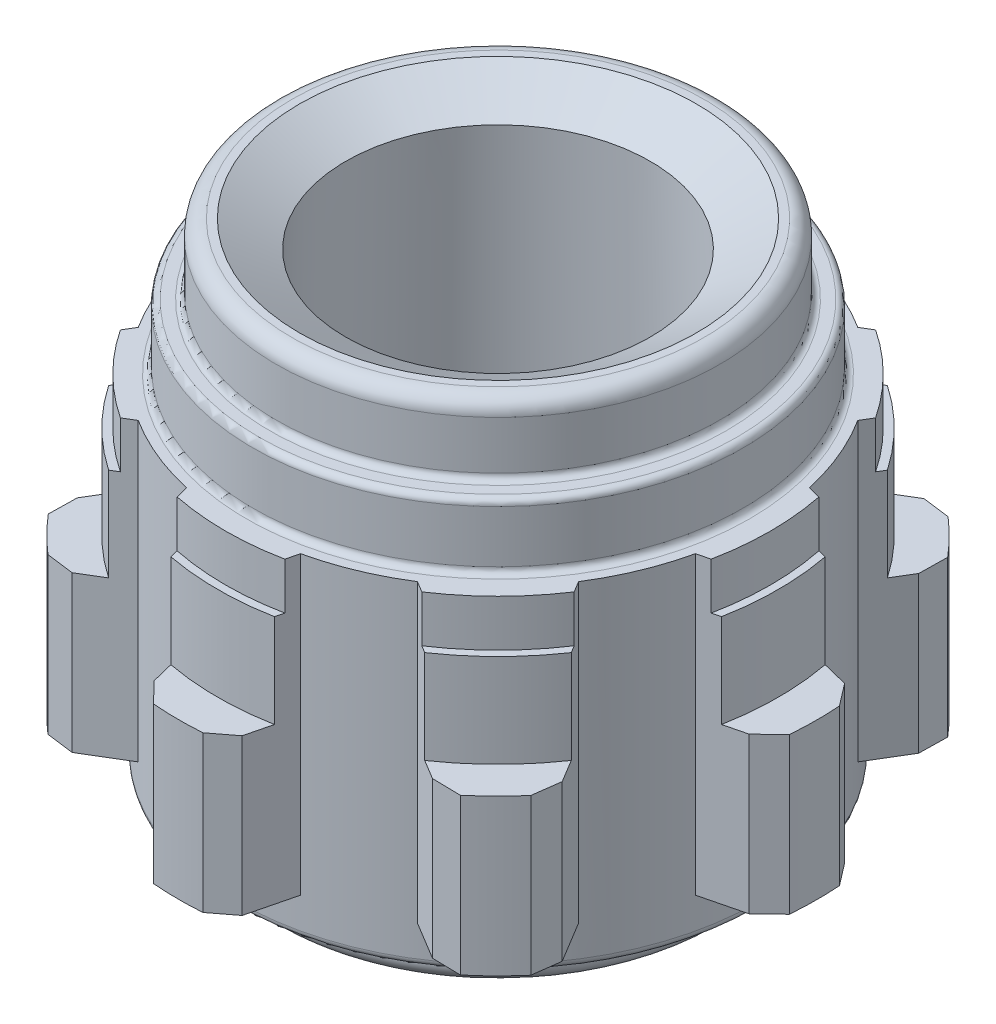
SolidWorks part; units mm, degrees
other "Câmera1"
ref_plane "Plano frontal" through (0, 0, 0) normal (0, 0, 1) x (1, 0, 0)
ref_plane "Plano superior" through (0, 0, 0) normal (0, 1, 0) x (1, 0, 0)
ref_plane "Plano direito" through (0, 0, 0) normal (1, 0, 0) x (0, 0, -1)
sketch "Esboço1" plane through (0, 0, 0) normal (0, 0, 1) x (1, 0, 0)
  line L0 (20.9097, -57.0834) -> (20.9097, 23.3) construction
  line L1 (40.4097, 23.3) -> (49.4097, 23.3)
  line L2 (49.4097, 23.3) -> (49.4097, 14.3)
  line L3 (49.4097, 14.3) -> (52.4097, 14.3)
  line L4 (52.4097, 14.3) -> (52.4097, 6)
  line L5 (52.4097, 6) -> (55.9097, 6)
  line L6 (55.9097, 6) -> (55.9097, 0)
  line L7 (55.9097, 0) -> (56.9097, 0)
  line L8 (56.9097, 0) -> (56.9097, -12)
  line L9 (56.9097, -12) -> (61.9097, -12)
  line L10 (61.9097, -12) -> (61.9097, -32)
  line L11 (61.9097, -32) -> (54.4097, -32)
  line L12 (54.4097, -32) -> (54.4097, -37)
  line L13 (54.4097, -37) -> (49.4097, -37)
  line L14 (49.4097, -37) -> (49.4097, -42)
  line L15 (49.4097, -42) -> (41.7996, -42)
  line L16 (41.7996, -42) -> (40.4097, 23.3)
  dimension "D1" = 19.5
  dimension "D2" = 28.5
  dimension "D3" = 31.5
  dimension "D4" = 35
  dimension "D5" = 36
  dimension "D6" = 41
  dimension "D7" = 33.5
  dimension "D8" = 28.5
  dimension "D9" = 9
  dimension "D10" = 8.3
  dimension "D11" = 6
  dimension "D12" = 12
  dimension "D13" = 20
  dimension "D14" = 5
  dimension "D15" = 5
revolve "Revolução1" add sketch "Esboço1" angle 360 about L0
sketch "Esboço2" plane through (0, -32, 0) normal (0, -1, 0) x (1, 0, 0)
  line L0 (20.9097, 0) -> (-27.9425, 0) construction
  line L1 (-20.1424, -5.25) -> (-20.1424, 5.25)
  line L2 (-20.1424, -5.25) -> (-11.6715, -7.35)
  line L3 (-11.8308, 25.3159) -> (-4.4062, 32.7405)
  line L4 (-20.1424, 5.25) -> (-11.6715, 7.35)
  line L5 (-4.4062, 32.7405) -> (3.0685, 28.2357)
  line L6 (-11.8308, 25.3159) -> (-7.3259, 17.8412)
  line L7 (15.6597, 41.0521) -> (26.1597, 41.0521)
  line L8 (26.1597, 41.0521) -> (28.2597, 32.5812)
  line L9 (15.6597, 41.0521) -> (13.5597, 32.5812)
  line L10 (46.2256, 32.7405) -> (53.6503, 25.3159)
  line L11 (53.6503, 25.3159) -> (49.1454, 17.8412)
  line L12 (46.2256, 32.7405) -> (38.7509, 28.2357)
  line L13 (61.9618, 5.25) -> (61.9618, -5.25)
  line L14 (61.9618, -5.25) -> (53.491, -7.35)
  line L15 (61.9618, 5.25) -> (53.491, 7.35)
  line L16 (53.6503, -25.3159) -> (46.2256, -32.7405)
  line L17 (46.2256, -32.7405) -> (38.7509, -28.2357)
  line L18 (53.6503, -25.3159) -> (49.1454, -17.8412)
  line L19 (26.1597, -41.0521) -> (15.6597, -41.0521)
  line L20 (15.6597, -41.0521) -> (13.5597, -32.5812)
  line L21 (26.1597, -41.0521) -> (28.2597, -32.5812)
  line L22 (-4.4062, -32.7405) -> (-11.8308, -25.3159)
  line L23 (-11.8308, -25.3159) -> (-7.3259, -17.8412)
  line L24 (-4.4062, -32.7405) -> (3.0685, -28.2357)
  circle A0 centre (20.9097, 0) radius 33.4
  circle M1 centre (20.9097, 0) radius 41
  circle M2 centre (20.9097, 0) radius 33.5
  dimension "D1" = 8
  dimension "D2" = 10.5
extrude "Corte-extrusão3" cut sketch "Esboço2" against normal through all contours L6 L4 M1 M2 | L9 L5 M1 M2 | L12 L8 M1 M2 | L15 L11 M1 M2 | L18 L14 M1 M2 | L21 L17 M1 M2 | L24 L20 M1 M2 | L23 L2 M1 M2
chamfer "Chanfro1" distance 2.5 angle 30 18 edges at (20.9097, -32, -41) (26.2595, -22, -40.6495) (20.9097, -12, -41) (15.5599, -22, -40.6495) (53.4361, -22, 24.9606) (45.8704, -22, 32.5264) (15.5599, -22, 40.6495) (26.2595, -22, 40.6495) (-4.0509, -22, 32.5264) (-11.6167, -22, 24.9606) (-19.7397, -22, 5.3498) (-19.7397, -22, -5.3498) (-11.6167, -22, -24.9606) (-4.0509, -22, -32.5264) (61.5592, -22, 5.3498) (61.5592, -22, -5.3498) (53.4361, -22, -24.9606) (45.8704, -22, -32.5264)
chamfer "Chanfro2" distance 6 angle 30 1 edges at (40.4097, 23.3, 0)
chamfer "Chanfro3" distance 6 angle 30 1 edges at (41.7996, -42, 0)
fillet "Filete2" radius 2 1 edges at (49.4097, 23.3, 0)
fillet "Filete3" radius 2 1 edges at (49.4097, -42, 0)
fillet "Filete4" radius 1 1 edges at (54.4097, -37, 0)
fillet "Filete5" radius 0.8 1 edges at (49.4097, -37, 0)
fillet "Filete6" radius 0.8 3 edges at (52.4097, 6, 0) (52.4097, 14.3, 0) (49.4097, 14.3, 0)
